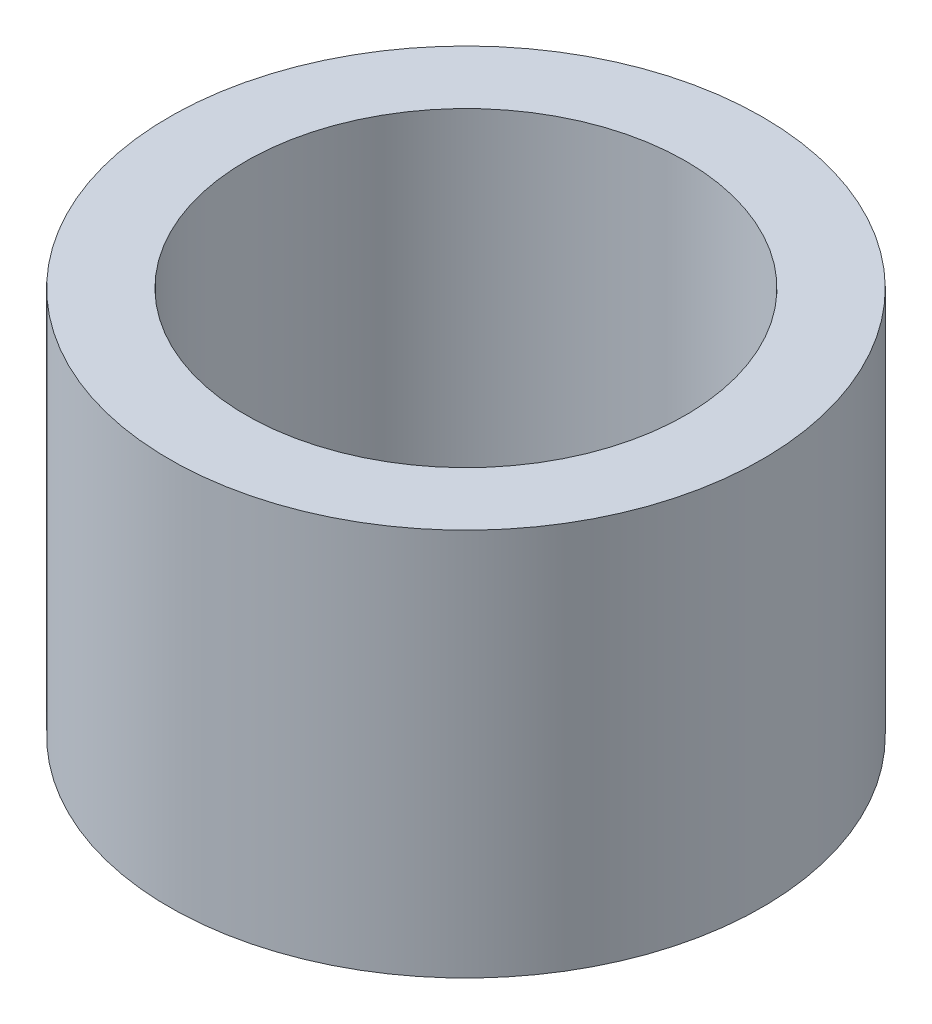
SolidWorks part; units mm, degrees
ref_plane "Front Plane" through (0, 0, 0) normal (0, 0, 1) x (1, 0, 0)
ref_plane "Top Plane" through (0, 0, 0) normal (0, 1, 0) x (1, 0, 0)
ref_plane "Right Plane" through (0, 0, 0) normal (1, 0, 0) x (0, 0, -1)
sketch "Sketch1" plane through (0, 0, 0) normal (0, 1, 0) x (1, 0, 0)
  circle A0 centre (0, 0) radius 10
  dimension "SLEEVE_OD" = 20
extrude "Boss-Extrude1" add sketch "Sketch1" along normal blind 13.0809
sketch "Sketch2" plane through (0, 0, 0) normal (0, 1, 0) x (1, 0, 0)
  circle A0 centre (0, 0) radius 7.4172
  dimension "BORE_D" = 14.8345
extrude "Cut-Extrude1" cut sketch "Sketch2" along normal through all
chamfer "Chamfer1" distance 1.7793 angle 61.354 rebuild error yes
